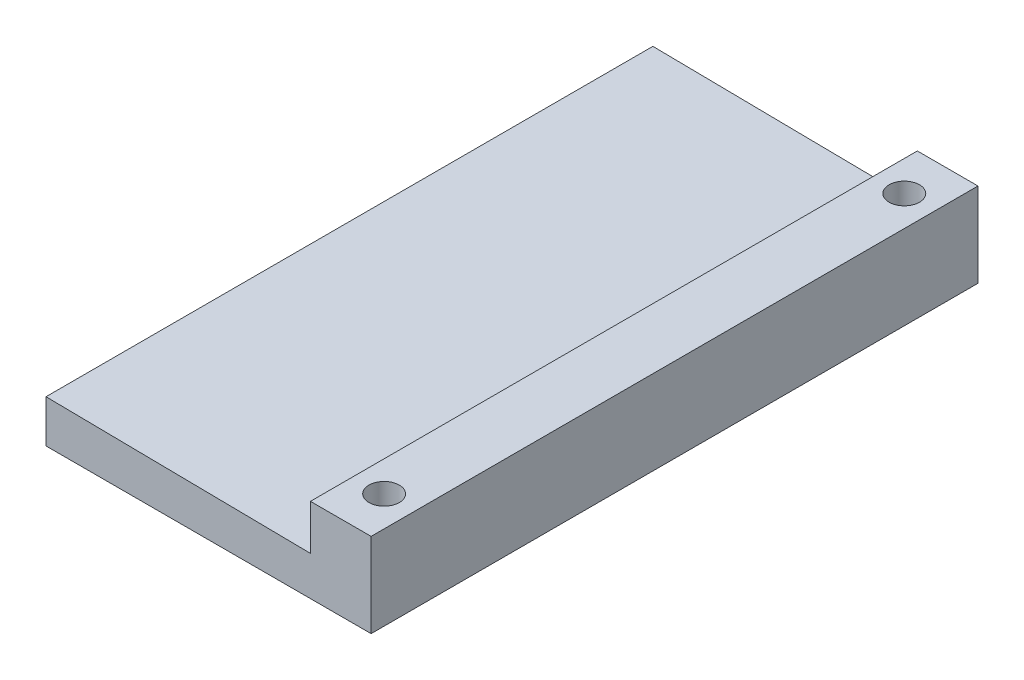
SolidWorks part; units mm, degrees
ref_plane "Front Plane" through (0, 0, 0) normal (0, 0, 1) x (1, 0, 0)
ref_plane "Top Plane" through (0, 0, 0) normal (0, 1, 0) x (1, 0, 0)
ref_plane "Right Plane" through (0, 0, 0) normal (1, 0, 0) x (0, 0, -1)
sketch "Sketch1" plane through (0, 0, 0) normal (0, 1, 0) x (1, 0, 0)
  line L1 (0, 0) -> (41.275, 0)
  line L2 (0, 0) -> (0, 88.9)
  line L3 (0, 88.9) -> (41.275, 88.9)
  line L4 (41.275, 0) -> (41.275, 88.9)
  line L5 (41.275, 88.9) -> (50.165, 88.9)
  line L6 (41.275, 88.9) -> (41.275, 0)
  line L7 (41.275, 0) -> (50.165, 0)
  line L8 (50.165, 88.9) -> (50.165, 0)
  dimension "D1" = 41.275
  dimension "D2" = 88.9
  dimension "D3" = 8.89
extrude "Boss-Extrude1" add sketch "Sketch1" along normal blind 5.9944 contours L1 L4 L3 L2 region at (20.6375, 0, -44.45)
extrude "Boss-Extrude2" add sketch "Sketch1<5>" along normal blind 12.3444 contours L8 L5 L4 L7 region at (45.72, 0, -44.45)
sketch "Sketch1<5>" plane through (0, 0, 0) normal (0, 1, 0) x (1, 0, 0) same geometry as "Sketch1"
sketch "Sketch3" plane through (0, 12.3444, 0) normal (0, 1, 0) x (1, 0, 0)
  line L0 (45.72, 82.55) -> (45.72, 6.35) construction
  line L1 (50.165, 88.9) -> (50.165, 0) construction
  line L2 (41.275, 88.9) -> (50.165, 88.9) construction
  line L3 (0, 0) -> (0, 88.9) construction
  circle A0 centre (45.72, 82.55) radius 2.2225
  circle A1 centre (45.72, 6.35) radius 2.2225
  point P4 (45.72, 44.45)
  point P6 (50.165, 44.45)
  point P7 (45.72, 88.9)
  dimension "D1" = 4.445
  dimension "D2" = 4.445
  dimension "D3" = 76.2
  dimension "D4" = 45.72
extrude "Cut-Extrude1" cut sketch "Sketch3" against normal through all both contours A1 | A0
sketch "Sketch4" plane through (0, 0, 0) normal (0, -1, 0) x (1, 0, 0)
  circle A0 centre (45.72, -6.35) radius 3.683
  circle A1 centre (45.72, -82.55) radius 3.683
  dimension "D1" = 7.366
  dimension "D2" = 7.366
extrude "Cut-Extrude2" cut sketch "Sketch4" against normal blind 4.064
sketch "Sketch5" plane through (0, 5.9944, 0) normal (0, 1, 0) x (1, 0, 0)
  line L0 (0, 0) -> (41.275, 0) construction
  line L1 (0, 88.9) -> (2.54, 88.9)
  line L2 (0, 88.9) -> (0, 0)
  line L3 (0, 0) -> (2.54, 0)
  line L4 (2.54, 88.9) -> (2.54, 0)
  dimension "D1" = 2.54
extrude "Cut-Extrude3" cut sketch "Sketch5" against normal through all both
sketch "Sketch6" plane through (0, 0, 0) normal (0, 0, 1) x (1, 0, 0)
  line L0 (2.54, 5.9944) -> (2.54, 6.2484)
  line L1 (2.54, 6.2484) -> (41.275, 5.7404)
  line L2 (2.54, 5.9944) -> (41.275, 5.9944)
  line L3 (41.275, 5.7404) -> (41.275, 5.9944)
  line M1 (41.275, 5.9944) -> (2.54, 5.9944)
  dimension "D1" = 0.254
  dimension "D2" = 0.254
extrude "Boss-Extrude3" add sketch "Sketch6" against normal up to surface (88.9 mm away) contours L1 L0 M1 region at (8.9958, 6.0791, 0) up to face at (31.3267, 6.1129, -88.9)
extrude "Cut-Extrude4" cut sketch "Sketch6<3>" against normal up to surface (88.9 mm away) contours L1 L3 M1 region at (34.8192, 5.9097, 0) up to face at (29.9811, 6.1323, -88.9)
sketch "Sketch6<3>" plane through (0, 0, 0) normal (0, 0, 1) x (1, 0, 0) same geometry as "Sketch6"
